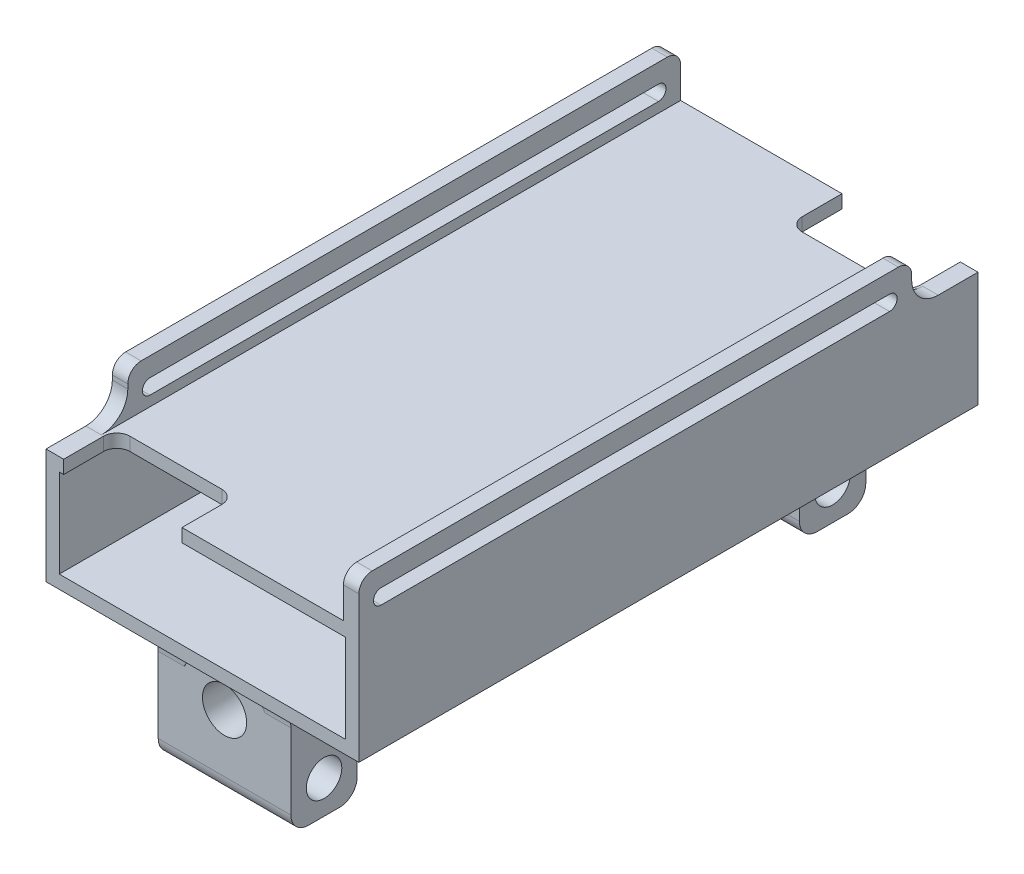
SolidWorks part; units mm, degrees
ref_plane "Front Plane" through (0, 0, 0) normal (0, 0, 1) x (1, 0, 0)
ref_plane "Top Plane" through (0, 0, 0) normal (0, 1, 0) x (1, 0, 0)
ref_plane "Right Plane" through (0, 0, 0) normal (1, 0, 0) x (0, 0, -1)
sketch "Sketch1" plane through (0, 0, 0) normal (0, 0, 1) x (1, 0, 0)
  line L1 (-32.375, 10) -> (32.375, 10)
  line L2 (-32.375, 10) -> (-32.375, -10)
  line L3 (-32.375, -10) -> (32.375, -10)
  line L4 (32.375, 10) -> (32.375, -10)
  line L5 (-32.375, 10) -> (32.375, -10) construction
  line L6 (-32.375, -10) -> (32.375, 10) construction
  point P0 (0, 0)
  dimension "D1" = 64.75
  dimension "D2" = 20
extrude "Body" add sketch "Sketch1" along normal blind 140
shell "Shell1" thickness 3 removed face at (0, 0, 0) removed face at (0, 0, 140) outward yes
sketch "Sketch2" plane through (0, 13, 0) normal (0, 1, 0) x (1, 0, 0)
  line L0 (-35.375, -140) -> (-35.375, 0) construction
  line L1 (4.625, 0) -> (31.375, 0)
  line L2 (4.625, 0) -> (4.625, -12)
  line L3 (4.625, -12) -> (31.375, -12)
  line L4 (31.375, 0) -> (31.375, -12)
  line L5 (-31.375, -140) -> (-4.625, -140)
  line L6 (-31.375, -140) -> (-31.375, -128)
  line L7 (-31.375, -128) -> (-4.625, -128)
  line L8 (-4.625, -140) -> (-4.625, -128)
  line L9 (35.375, -140) -> (35.375, 0) construction
  line L10 (35.375, -140) -> (-35.375, -140) construction
  line L11 (35.375, 0) -> (-35.375, 0) construction
  dimension "D1" = 12
  dimension "D2" = 40
  dimension "D3" = 40
  dimension "D4" = 4
  dimension "D5" = 4
extrude "Switch_cutout" cut sketch "Sketch2" against normal up to next
ref_plane "Plane1" through (0, 0, 0) normal (-1, 0, 0) x (0, 0, 1)
sketch "Sketch4" plane through (0, 0, 0) normal (-1, 0, 0) x (0, 0, 1)
  line L0 (70, -19.8206) -> (70, -43.8873) construction
  line L1 (5, -13) -> (20, -13)
  line L2 (5, -13) -> (5, -40)
  line L3 (5, -40) -> (20, -40)
  line L4 (20, -13) -> (20, -40)
  line L9 (140, 13) -> (0, 13) construction
  line L10 (140, -13) -> (0, -13) construction
  line L11 (135, -40) -> (120, -40)
  line L12 (120, -13) -> (120, -40)
  line L13 (135, -13) -> (135, -40)
  line L14 (135, -13) -> (120, -13)
  line L15 (0, 13) -> (0, -13) construction
  circle A1 centre (12.5, -32.5) radius 4.0125
  circle A2 centre (127.5, -32.5) radius 4.0125
  point P16 (12.5, -40)
  point P17 (70, 13)
  dimension "D1" = 8.025
  dimension "D2" = 15
  dimension "D3" = 27
  dimension "D4" = 7.5
  dimension "D5" = 5
extrude "Axle_holder" add sketch "Sketch4" along normal mid plane 30
sketch "Sketch5" plane through (0, 0, 0) normal (-1, 0, 0) x (0, 0, 1)
  circle A0 centre (12.5, -32.5) radius 2.5
  circle A1 centre (127.5, -32.5) radius 2.5
  circle A2 centre (12.5, -32.5) radius 4.0125 construction
  circle A4 centre (12.5, -32.5) radius 4.0125
  circle A5 centre (127.5, -32.5) radius 4.0125
  circle A7 centre (127.5, -32.5) radius 4.0125 construction
  dimension "D1" = 5
extrude "Bushing_holder" add sketch "Sketch5" along normal mid plane 18
fillet "Fillet3" radius 4 4 edges at (0, -40, 5) (0, -40, 20) (0, -40, 135) (0, -40, 120)
fillet "Fillet4" radius 6 4 edges at (0, -13, 20) (0, -13, 135) (0, -13, 5) (0, -13, 120)
sketch "Sketch6" plane through (35.375, 0, 0) normal (1, 0, 0) x (0, 0, -1)
  line L0 (-135, 17) -> (-20, 17) construction
  line L1 (-140, 13) -> (-15, 13)
  line L2 (-140, 13) -> (-140, 23)
  line L3 (-140, 23) -> (-15, 23)
  line L4 (-15, 13) -> (-15, 23)
  line L5 (-135, 18.7) -> (-20, 18.7)
  line L6 (-135, 15.3) -> (-20, 15.3)
  line L7 (-140, -13) -> (-140, 13) construction
  line L8 (0, -13) -> (0, 13) construction
  line L9 (-140, 13) -> (0, 13) construction
  arc A0 (-135, 18.7) -> (-135, 15.3) centre (-135, 17) ccw
  arc A1 (-20, 15.3) -> (-20, 18.7) centre (-20, 17) ccw
  point P5 (-77.5, 17)
  dimension "D2" = 1.7
  dimension "D1" = 10
  dimension "D3" = 5
  dimension "D4" = 5
  dimension "D5" = 4
  dimension "D6" = 15
extrude "Slide_mount" add sketch "Sketch6" against normal blind 3.5
ref_plane "Plane2" through (0, 0, 0) normal (1, 0, 0) x (0, 0, -1)
ref_plane "Plane3" through (0, 0, 70) normal (0, 0, 1) x (1, 0, 0)
ref_axis "Axis1" through (0, -14.65, 70) along (0, 1, 0)
pattern_circular "CirPattern1" count 2 over 360 about axis through (0, -14.65, 70) along (0, 1, 0) of "Slide_mount"
fillet "Fillet6" radius 3 4 edges at (33.625, 23, 140) (33.625, 23, 15) (-33.625, 23, 0) (-33.625, 23, 125)
fillet "Fillet7" radius 3 4 edges at (31.375, 11.5, 12) (4.625, 11.5, 12) (-4.625, 11.5, 128) (-31.375, 11.5, 128)
fillet "Fillet8" radius 6 2 edges at (33.625, 13, 15) (-33.625, 13, 125)
sketch "Sketch7" plane through (0, 0, 135) normal (0, 0, 1) x (1, 0, 0)
  line L1 (15, -18.9161) -> (-15, -18.9161) construction
  circle A0 centre (0, -22.9161) radius 5
  point P2 (0.7875, -23.638)
  point P3 (0, -28.4559)
  point P6 (0, -18.9161)
  dimension "D1" = 10
  dimension "D2" = 4
extrude "Cut-Extrude1" cut sketch "Sketch7" against normal up to next
sketch "Sketch8" plane through (0, 0, 135) normal (0, 0, 1) x (1, 0, 0)
  line L0 (-15, -13) -> (15, -13) construction
  circle A0 centre (0, -22.9161) radius 9.9161
  arc A1 (-3, -18.9161) -> (3, -18.9161) centre (0, -22.9161) ccw construction
extrude "Cut-Extrude2" cut sketch "Sketch8" along normal blind 9
sketch "Sketch9" plane through (0, 0, 120) normal (0, 0, -1) x (-1, 0, 0)
  line L1 (-6.6973, -22.9161) -> (-3.3486, -28.7161)
  line L2 (-3.3486, -28.7161) -> (3.3486, -28.7161)
  line L3 (3.3486, -28.7161) -> (6.6973, -22.9161)
  line L4 (6.6973, -22.9161) -> (3.3486, -17.1161)
  line L5 (3.3486, -17.1161) -> (-3.3486, -17.1161)
  line L6 (-3.3486, -17.1161) -> (-6.6973, -22.9161)
  circle A0 centre (0, -22.9161) radius 5.8 construction
  arc A1 (-3.1087, -19) -> (3.1087, -19) centre (0, -22.9161) ccw construction
  point P1 (0, 0)
  dimension "D1" = 11.6
extrude "Cut-Extrude3" cut sketch "Sketch9" against normal mid plane 7
